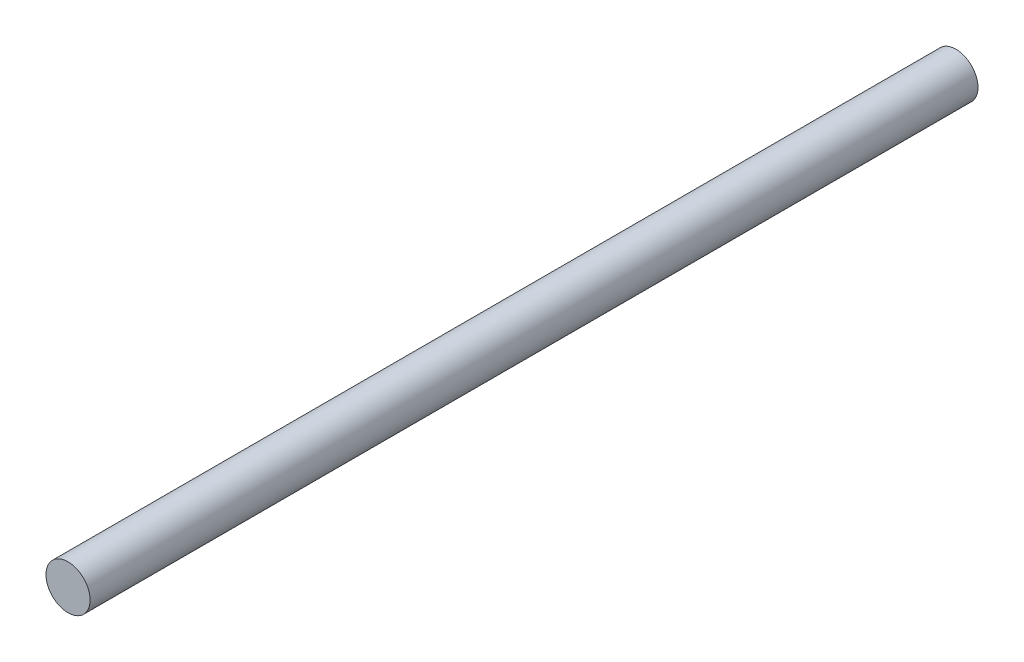
SolidWorks part; units mm, degrees
ref_plane "Front Plane" through (0, 0, 0) normal (0, 0, 1) x (1, 0, 0)
ref_plane "Top Plane" through (0, 0, 0) normal (0, 1, 0) x (1, 0, 0)
ref_plane "Right Plane" through (0, 0, 0) normal (1, 0, 0) x (0, 0, -1)
sketch "Sketch1" plane through (0, 0, 0) normal (0, 0, 1) x (1, 0, 0)
  circle A0 centre (0, 0) radius 1.94
  dimension "D1" = 3.88
extrude "Boss-Extrude1" add sketch "Sketch1" along normal blind 78
